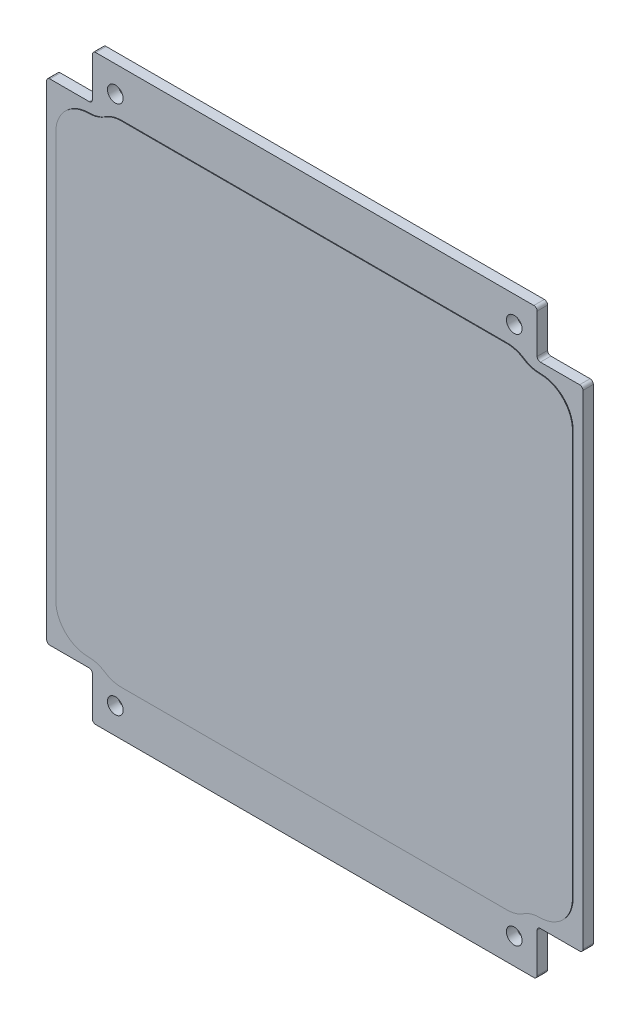
SolidWorks part; units mm, degrees
material "PET"
ref_plane "Front Plane" through (0, 0, 0) normal (0, 0, 1) x (1, 0, 0)
ref_plane "Top Plane" through (0, 0, 0) normal (0, 1, 0) x (1, 0, 0)
ref_plane "Right Plane" through (0, 0, 0) normal (1, 0, 0) x (0, 0, -1)
sketch "Sketch1" plane through (0, 0, 0) normal (0, 0, 1) x (1, 0, 0)
  line L0 (-34, 44) -> (-34, 38)
  line L1 (-33.5, -44.5) -> (33.5, -44.5)
  line L2 (-41, 37) -> (-41, -37)
  line L3 (-33.5, 44.5) -> (33.5, 44.5)
  line L4 (41, -37) -> (41, 37)
  line L5 (34, -44) -> (34, -38)
  line L6 (34.5, -37.5) -> (40.5, -37.5)
  line L7 (-34.5, 37.5) -> (-40.5, 37.5)
  line L8 (34, 44) -> (34, 38)
  line L9 (34.5, 37.5) -> (40.5, 37.5)
  line L10 (-40.5, -37.5) -> (-34.5, -37.5)
  line L11 (-34, -38) -> (-34, -44)
  line L12 (-34.5, -38) -> (34.5, 38) construction
  line L13 (34.5, -38) -> (-34.5, 38) construction
  arc A0 (-33.5, 44.5) -> (-34, 44) centre (-33.5, 44) ccw
  arc A1 (33.5, 44.5) -> (34, 44) centre (33.5, 44) cw
  arc A2 (34, 38) -> (34.5, 37.5) centre (34.5, 38) ccw
  arc A3 (40.5, 37.5) -> (41, 37) centre (40.5, 37) cw
  arc A4 (33.5, -44.5) -> (34, -44) centre (33.5, -44) ccw
  arc A5 (34.5, -37.5) -> (34, -38) centre (34.5, -38) ccw
  arc A6 (40.5, -37.5) -> (41, -37) centre (40.5, -37) ccw
  arc A7 (-34, -44) -> (-33.5, -44.5) centre (-33.5, -44) ccw
  arc A8 (-34, -38) -> (-34.5, -37.5) centre (-34.5, -38) ccw
  arc A9 (-41, -37) -> (-40.5, -37.5) centre (-40.5, -37) ccw
  arc A10 (-40.5, 37.5) -> (-41, 37) centre (-40.5, 37) ccw
  arc A11 (-34.5, 37.5) -> (-34, 38) centre (-34.5, 38) ccw
  point P0 (0, 0)
  dimension "D4" = 0.5
  dimension "D1" = 7
  dimension "D2" = 7
  dimension "D3" = 7
  dimension "D5" = 7
  dimension "D6" = 7
  dimension "D7" = 7
  dimension "D8" = 7
  dimension "D9" = 7
  dimension "D10" = 89
  dimension "D11" = 82
extrude "Boss-Extrude1" add sketch "Sketch1" along normal blind 1.6
sketch "Esboço1" plane through (0, 0, 1.6) normal (0, 0, 1) x (1, 0, 0)
  line L0 (11.8117, 0) -> (-11.978, 0) construction
  line L1 (-29.5, -37.5) -> (29.5, -37.5)
  line L2 (0, 10.1561) -> (0, -5.0161) construction
  line L3 (-29.5, 37.5) -> (29.5, 37.5)
  line L5 (-29.5, -32.5) -> (29.5, 32.5) construction
  line L6 (-29.5, 32.5) -> (29.5, -32.5) construction
  line L8 (-39.5, -31) -> (-39.5, 31)
  line L10 (39.5, -31) -> (39.5, 31)
  line L11 (-39.5, -36) -> (39.5, 36) construction
  line L12 (-39.5, 36) -> (39.5, -36) construction
  arc A0 (-34.5, 36) -> (-32, 36.75) centre (-34.5, 40.5417) ccw
  arc A1 (-29.5, 37.5) -> (-32, 36.75) centre (-29.5, 32.9583) ccw
  arc A2 (-29.5, -37.5) -> (-32, -36.75) centre (-29.5, -32.9583) cw
  arc A3 (-34.5, -36) -> (-32, -36.75) centre (-34.5, -40.5417) cw
  arc A4 (34.5, 36) -> (39.5, 31) centre (34.5, 31) cw
  arc A5 (34.5, -36) -> (39.5, -31) centre (34.5, -31) ccw
  arc A6 (-34.5, -36) -> (-39.5, -31) centre (-34.5, -31) cw
  arc A7 (-39.5, 31) -> (-34.5, 36) centre (-34.5, 31) cw
  arc A8 (29.5, -37.5) -> (32, -36.75) centre (29.5, -32.9583) ccw
  arc A9 (34.5, -36) -> (32, -36.75) centre (34.5, -40.5417) ccw
  arc A10 (29.5, 37.5) -> (32, 36.75) centre (29.5, 32.9583) cw
  arc A11 (34.5, 36) -> (32, 36.75) centre (34.5, 40.5417) cw
  point P0 (0, 0)
  point P1 (0, 0)
  dimension "D2" = 5
  dimension "D3" = 75
  dimension "D5" = 79
extrude "Boss-Extrude2" add sketch "Esboço1" along normal blind 0.1
hole_wizard "M2 Hole1-FixingStructure" positions "Sketch3" profile "Sketch2" hole size "M2" standard "DIN"
sketch "Sketch3" plane through (0, 0, 0) normal (0, 0, -1) x (-1, 0, 0)
  line L0 (-33.5, 44.5) -> (33.5, 44.5) construction
  line L1 (33.5, -44.5) -> (-33.5, -44.5) construction
  line L2 (-41, -37) -> (-41, 37) construction
  line L3 (41, 37) -> (41, -37) construction
  point P0 (-30.5, 40.5)
  point P2 (30.5, 40.5)
  point P4 (-30.5, -40.5)
  point P6 (30.5, -40.5)
  dimension "D1" = 4
  dimension "D2" = 4
  dimension "D3" = 10.5
  dimension "D4" = 10.5
sketch "Sketch2" plane through (30.5, 40.5, 0) normal (1, 0, 0) x (0, 1, 0)
  line L0 (0, 0) -> (0, 200.721)
  line L1 (0, 200.721) -> (1.2, 200)
  line L2 (1.2, 200) -> (1.2, 0)
  line L5 (1.2, 0) -> (0, 0)
  line L10 (0, 200.721) -> (-1.2, 200) construction
  line L11 (0, -6.35) -> (0, 107.95) construction
  dimension "Hole Dia." = 2.4
  dimension "Hole Depth" = 200
  dimension "Drill Angle" = 118
